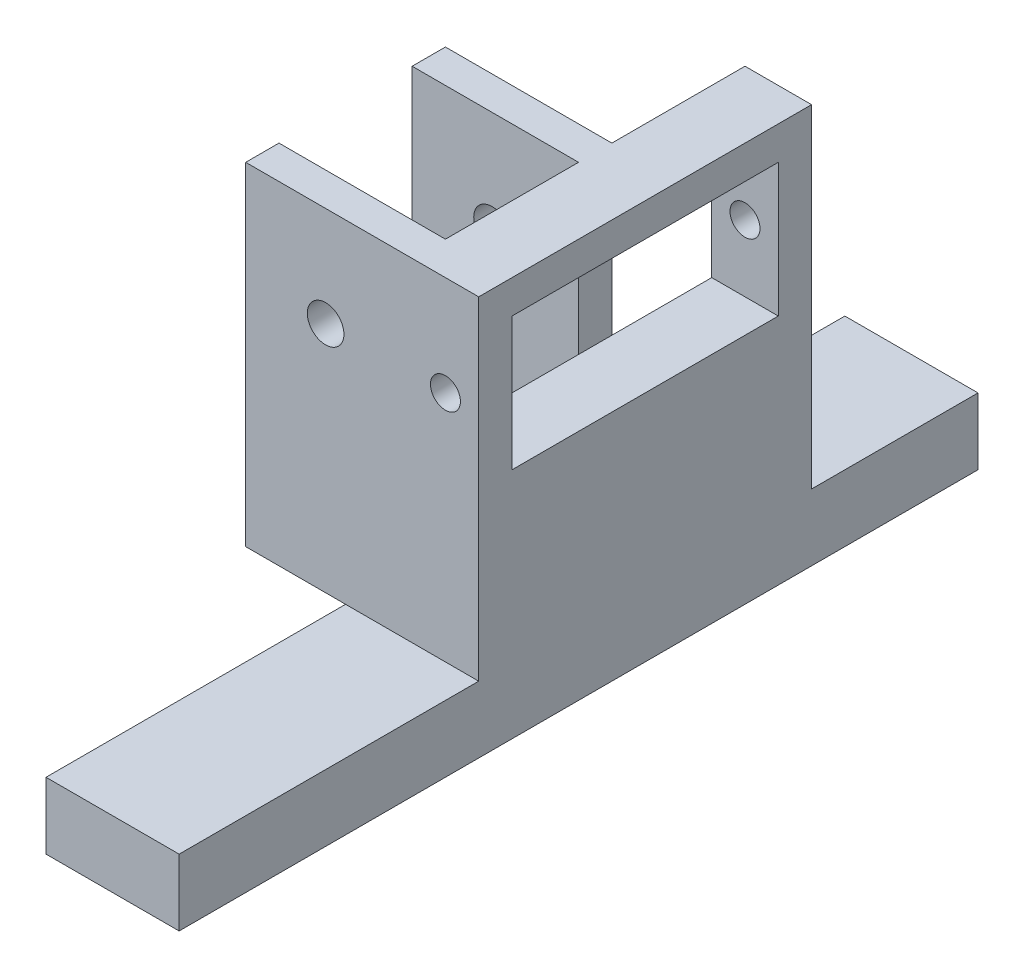
SolidWorks part; units mm, degrees
ref_plane "Front Plane" through (0, 0, 0) normal (0, 0, 1) x (1, 0, 0)
ref_plane "Top Plane" through (0, 0, 0) normal (0, 1, 0) x (1, 0, 0)
ref_plane "Right Plane" through (0, 0, 0) normal (1, 0, 0) x (0, 0, -1)
sketch "Sketch4" plane through (0, 0, 0) normal (0, 1, 0) x (1, 0, 0)
  line L1 (0, 0) -> (40, 0)
  line L2 (0, 0) -> (0, 80)
  line L3 (0, 80) -> (40, 80)
  line L4 (40, 0) -> (40, 80)
  dimension "D1" = 80
  dimension "D2" = 40
extrude "Boss-Extrude4" add sketch "Sketch4" along normal blind 5
sketch "Sketch5" plane through (0, 5, 0) normal (0, 1, 0) x (1, 0, 0)
  line L0 (40, 40) -> (30, 40)
  line L1 (30, 30) -> (30, 50) construction
  line L2 (40, 50) -> (30, 50)
  line L3 (30, 50) -> (30, 55)
  line L4 (0, 80) -> (0, 0)
  line L5 (0, 0) -> (40, 0)
  line L6 (40, 0) -> (40, 80)
  line L7 (40, 80) -> (0, 80)
  line L8 (0, 80) -> (0, 0)
  line L9 (0, 0) -> (40, 0)
  line L10 (40, 0) -> (40, 80)
  line L11 (40, 80) -> (0, 80)
  line L12 (30, 55) -> (40, 55)
  line L13 (40, 55) -> (40, 50)
  line L14 (40, 30) -> (30, 30)
  line L15 (30, 30) -> (30, 25)
  line L16 (30, 25) -> (40, 25)
  line L17 (40, 25) -> (40, 30)
  point P9 (30, 40)
  line M11 (40, 0) -> (40, 80)
  dimension "D2" = 10
  dimension "D3" = 10
  dimension "D4" = 5
  dimension "D5" = 5
  dimension "D1" = 0
extrude "Boss-Extrude6" add sketch "Sketch5" along normal blind 50 contours L12 L3 L2 M11 | L15 L16 L10 L14 region at (35, 5, -52.5) region at (35, 5, -27.5)
sketch "Sketch7" plane through (0, 0, -50) normal (0, 0, 1) x (1, 0, 0)
  line L1 (30, 5) -> (40, 5)
  line L2 (30, 5) -> (30, 30)
  line L3 (30, 30) -> (40, 30)
  line L4 (40, 5) -> (40, 30)
  line L5 (40, 55) -> (40, 5) construction
  line L7 (30, 55) -> (40, 55)
  line L8 (30, 55) -> (30, 50)
  line L9 (30, 50) -> (40, 50)
  line L10 (40, 55) -> (40, 50)
  dimension "D1" = 25
  dimension "D2" = 10
  dimension "D3" = 5
extrude "Boss-Extrude7" add sketch "Sketch7" along normal up to surface (20 mm away) contours L8 L7 L10 L9 | L2 L1 L4 L3 up to face at (35, 30, -30)
sketch "Sketch9" plane through (0, 0, 0) normal (-1, 0, 0) x (0, 0, 1)
  line L4 (-80, 0) -> (0, 0)
  line L5 (0, 0) -> (0, 5)
  line L6 (0, 5) -> (-80, 5)
  line L7 (-80, 5) -> (-80, 0)
  line L8 (-80, 0) -> (0, 0)
  line L9 (0, 0) -> (0, 5)
  line L10 (0, 5) -> (-80, 5)
  line L12 (-80, 5) -> (-80, 0)
  dimension "D1" = 0
extrude "Boss-Extrude9" add sketch "Sketch9" along normal blind 10
sketch "Sketch10" plane through (0, 0, 0) normal (0, 0, 1) x (1, 0, 0)
  line L4 (-10, 0) -> (40, 0)
  line L5 (40, 0) -> (40, 5)
  line L6 (40, 5) -> (-10, 5)
  line L7 (-10, 5) -> (-10, 0)
  line L8 (-10, 0) -> (40, 0)
  line L9 (40, 0) -> (40, 5)
  line L10 (40, 5) -> (-10, 5)
  line L11 (-10, 5) -> (-10, 0)
  dimension "D1" = 0
extrude "Boss-Extrude10" add sketch "Sketch10" along normal blind 20
sketch "Sketch11" plane through (0, 0, -50) normal (0, 0, 1) x (1, 0, 0)
  line L0 (30, 40) -> (35, 40)
  line L4 (30, 30) -> (40, 30)
  line L5 (40, 30) -> (40, 50)
  line L6 (40, 50) -> (30, 50)
  line L7 (30, 50) -> (30, 30)
  line L8 (30, 30) -> (40, 30)
  line L9 (40, 30) -> (40, 50)
  line L10 (40, 50) -> (30, 50)
  line L11 (30, 50) -> (30, 30)
  circle A0 centre (35, 40) radius 2.25
  dimension "D3" = 4.5
  dimension "D2" = 5
  dimension "D1" = 0
extrude "Cut-Extrude1" cut sketch "Sketch11" against normal mid plane 50 contours A0 region at (35, 42.1864, -50)
sketch "Sketch12" plane through (0, 0, -25) normal (0, 0, 1) x (1, 0, 0)
  circle A0 centre (35, 40) radius 2.25 construction
  circle A1 centre (35, 40) radius 2.25
  circle A2 centre (35, 40) radius 4
  dimension "D1" = 8
extrude "Cut-Extrude2" cut sketch "Sketch12" against normal blind 2
sketch "Sketch15" plane through (30, 0, 0) normal (-1, 0, 0) x (0, 0, 1)
  line L1 (-55, 55) -> (-50, 55)
  line L2 (-55, 55) -> (-55, 5)
  line L3 (-55, 5) -> (-50, 5)
  line L4 (-50, 55) -> (-50, 5)
  line L5 (-25, 55) -> (-30, 55)
  line L6 (-25, 55) -> (-25, 5)
  line L7 (-25, 5) -> (-30, 5)
  line L8 (-30, 55) -> (-30, 5)
  dimension "D1" = 50
  dimension "D2" = 5
  dimension "D3" = 50
  dimension "D4" = 5
extrude "Boss-Extrude11" add sketch "Sketch15" along normal blind 20
sketch "Sketch16" plane through (0, 0, -25) normal (0, 0, 1) x (1, 0, 0)
  line L0 (35, 40) -> (17, 40)
  circle A0 centre (35, 40) radius 4 construction
  circle A1 centre (35, 40) radius 4
  circle A2 centre (17, 40) radius 2.75
  dimension "D2" = 5.5
  dimension "D1" = 18
extrude "Cut-Extrude4" cut sketch "Sketch16" against normal up to surface (30 mm away) contours A2 region at (14.3278, 40, -25) up to face at (32.75, 40, -55)
sketch "Sketch19" plane through (10, 0, 0) normal (-1, 0, 0) x (0, 0, 1)
  line L4 (-55, 55) -> (-55, 5)
  line L5 (-55, 5) -> (-50, 5)
  line L6 (-50, 5) -> (-50, 55)
  line L7 (-50, 55) -> (-55, 55)
  line L8 (-55, 55) -> (-55, 5)
  line L10 (-50, 5) -> (-50, 55)
  line L11 (-50, 55) -> (-55, 55)
  line L12 (-25, 5) -> (-25, 55)
  line L13 (-25, 55) -> (-30, 55)
  line L14 (-30, 55) -> (-30, 5)
  line L15 (-30, 5) -> (-25, 5)
  line L16 (-25, 5) -> (-25, 55)
  line L17 (-25, 55) -> (-30, 55)
  line L18 (-30, 55) -> (-30, 5)
  line L20 (-55, 5) -> (-50, 5)
  line L21 (-30, 5) -> (-25, 5)
  dimension "D1" = 0
  dimension "D2" = 0
extrude "Boss-Extrude12" add sketch "Sketch19" along normal blind 5
sketch "Sketch21" plane through (0, 0, 0) normal (0, -1, 0) x (1, 0, 0)
  line L4 (40, -80) -> (40, 20)
  line L5 (40, 20) -> (-10, 20)
  line L6 (-10, 20) -> (-10, -80)
  line L7 (-10, -80) -> (40, -80)
  line L8 (40, -80) -> (40, 20)
  line L9 (40, 20) -> (-10, 20)
  line L10 (-10, 20) -> (-10, -80)
  line L11 (-10, -80) -> (40, -80)
  dimension "D1" = 0
extrude "Boss-Extrude14" add sketch "Sketch21" along normal blind 5
sketch "Sketch22" plane through (0, 0, -80) normal (0, 0, -1) x (-1, 0, 0)
  line L4 (-40, 5) -> (-40, -5)
  line L5 (-40, -5) -> (10, -5)
  line L6 (10, -5) -> (10, 5)
  line L7 (10, 5) -> (-40, 5)
  line L8 (-40, 5) -> (-40, -5)
  line L9 (-40, -5) -> (10, -5)
  line L10 (10, -5) -> (10, 5)
  line L11 (10, 5) -> (-40, 5)
  dimension "D1" = 0
extrude "Boss-Extrude15" add sketch "Sketch22" along normal blind 20
sketch "Sketch24" plane through (0, 55, 0) normal (0, 1, 0) x (1, 0, 0)
  line L1 (5, 55) -> (40, 55)
  line L2 (5, 55) -> (5, 50)
  line L3 (5, 50) -> (40, 50)
  line L4 (40, 55) -> (40, 50)
  line L5 (40, 25) -> (40, 55) construction
  dimension "D1" = 35
  dimension "D2" = 5
extrude "Cut-Extrude5" cut sketch "Sketch24" against normal blind 50
sketch "Sketch25" plane through (0, 0, -50) normal (0, 0, -1) x (-1, 0, 0)
  line L4 (-30, 5) -> (-30, 30)
  line L5 (-30, 30) -> (-40, 30)
  line L6 (-40, 30) -> (-40, 5)
  line L7 (-40, 5) -> (-30, 5)
  line L8 (-30, 5) -> (-30, 30)
  line L9 (-30, 30) -> (-40, 30)
  line L10 (-40, 30) -> (-40, 5)
  line L11 (-40, 5) -> (-30, 5)
  line L12 (-30, 50) -> (-30, 55)
  line L13 (-30, 55) -> (-40, 55)
  line L14 (-40, 55) -> (-40, 50)
  line L15 (-40, 50) -> (-30, 50)
  line L16 (-30, 50) -> (-30, 55)
  line L17 (-30, 55) -> (-40, 55)
  line L18 (-40, 55) -> (-40, 50)
  line L19 (-40, 50) -> (-30, 50)
  dimension "D1" = 0
  dimension "D2" = 0
extrude "Boss-Extrude16" add sketch "Sketch25" along normal blind 25
sketch "Sketch26" plane through (0, 30, 0) normal (0, 1, 0) x (1, 0, 0)
  line L1 (40, 75) -> (30, 75)
  line L2 (40, 75) -> (40, 70)
  line L3 (40, 70) -> (30, 70)
  line L4 (30, 75) -> (30, 70)
  line L5 (30, 30) -> (30, 75) construction
  dimension "D1" = 5
  dimension "D2" = 10
extrude "Boss-Extrude17" add sketch "Sketch26" along normal blind 20
sketch "Sketch27" plane through (0, 0, -27) normal (0, 0, 1) x (1, 0, 0)
  circle A0 centre (35, 40) radius 2.25 construction
  circle A1 centre (35, 40) radius 4
  circle A2 centre (35, 40) radius 4
  circle A3 centre (35, 40) radius 2.25
  dimension "D1" = 0
extrude "Boss-Extrude18" add sketch "Sketch27" along normal up to surface (2 mm away) up to face at (19.75, 40, -25)
sketch "Sketch28" plane through (0, 0, -25) normal (0, 0, 1) x (1, 0, 0)
  circle A0 centre (35, 40) radius 2.25 construction
  circle A1 centre (35, 40) radius 2.25
extrude "Cut-Extrude6" cut sketch "Sketch28" against normal blind 50
sketch "Sketch29" plane through (0, 5, 0) normal (0, 1, 0) x (1, 0, 0)
  line L0 (5, 30) -> (5, 50) construction
  line L2 (5, 50) -> (30, 50)
  line L3 (5, 50) -> (5, 55)
  line L4 (5, 55) -> (30, 55)
  line L5 (30, 50) -> (30, 55)
  line L6 (30, 30) -> (30, 75) construction
  dimension "D1" = 20
  dimension "D2" = 5
  dimension "D3" = 25
extrude "Boss-Extrude19" add sketch "Sketch29" along normal up to surface (50 mm away) contours L3 L2 L5 L4 up to face at (25, 55, -43.3333)
sketch "Sketch31" plane through (0, 0, -25) normal (0, 0, 1) x (1, 0, 0)
  circle A0 centre (17, 40) radius 2.75 construction
  circle A1 centre (17, 40) radius 2.75
extrude "Cut-Extrude7" cut sketch "Sketch31" against normal blind 30
sketch "Sketch32" plane through (0, 5, 0) normal (0, 1, 0) x (1, 0, 0)
  line L0 (-10, 100) -> (40, 100) construction
  line L1 (20, 100) -> (-10, 100)
  line L2 (20, 100) -> (20, 55)
  line L3 (20, 55) -> (-10, 55)
  line L4 (-10, 100) -> (-10, 55)
  line L5 (20, 480) -> (20, -20) construction
  line L6 (-10, -20) -> (-10, 100) construction
  line L7 (5, 25) -> (40, 25) construction
  line L8 (-10, -20) -> (20, -20)
  line L9 (-10, -20) -> (-10, 25)
  line L10 (-10, 25) -> (20, 25)
  line L11 (20, -20) -> (20, 25)
  dimension "D1" = 45
  dimension "D2" = 30
extrude "Cut-Extrude8" cut sketch "Sketch32" against normal blind 10
sketch "Sketch33" plane through (-10, 0, 0) normal (-1, 0, 0) x (0, 0, 1)
  line L4 (-55, 5) -> (-55, -5)
  line L5 (-55, -5) -> (-25, -5)
  line L6 (-25, -5) -> (-25, 5)
  line L7 (-25, 5) -> (-55, 5)
  line L8 (-55, 5) -> (-55, -5)
  line L9 (-55, -5) -> (-25, -5)
  line L10 (-25, -5) -> (-25, 5)
  line L11 (-25, 5) -> (-55, 5)
  dimension "D1" = 0
extrude "Cut-Extrude9" cut sketch "Sketch33" against normal up to surface (30 mm away) up to face at (20, 0, -2.5)
